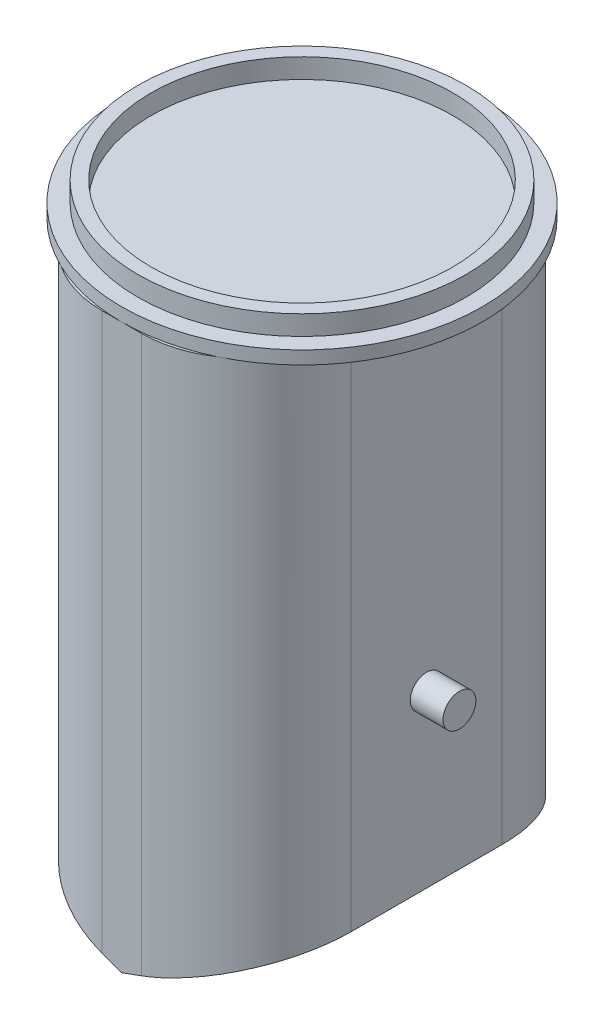
SolidWorks part; units mm, degrees
material "Galvanized Steel"
ref_plane "Front Plane" through (0, 0, 0) normal (0, 0, 1) x (1, 0, 0)
ref_plane "Top Plane" through (0, 0, 0) normal (0, 1, 0) x (1, 0, 0)
ref_plane "Right Plane" through (0, 0, 0) normal (1, 0, 0) x (0, 0, -1)
sketch "Sketch1" plane through (0, 0, 0) normal (0, 1, 0) x (1, 0, 0)
  circle A0 centre (0, 0) radius 27.5
  dimension "D1" = 55
extrude "Boss-Extrude1" add sketch "Sketch1" along normal blind 2
sketch "Sketch2" plane through (0, 2, 0) normal (0, 1, 0) x (1, 0, 0)
  circle A0 centre (0, 0) radius 25
  circle A1 centre (0, 0) radius 23
  dimension "D1" = 50
  dimension "D2" = 46
extrude "Boss-Extrude2" add sketch "Sketch2" along normal blind 3 contours A1
sketch "Sketch3" plane through (0, 0, 0) normal (0, -1, 0) x (1, 0, 0)
  line L5 (19, -27.5) -> (-19, 27.5) construction
  line L6 (33.4253, 0) -> (-33.4253, 0) construction
  line L7 (3, -27.5) -> (-3, -27.5)
  line L8 (19, -11.5) -> (19, 11.5)
  line L9 (3, 27.5) -> (-3, 27.5)
  line L10 (-19, -11.5) -> (-19, 11.5)
  line L11 (19, -27.5) -> (-19, 27.5) construction
  line L12 (19, 27.5) -> (-19, -27.5) construction
  circle A4 centre (0, 0) radius 27.5 construction
  arc A5 (3, -27.5) -> (19, -11.5) centre (3, -11.5) ccw
  arc A6 (-3, -27.5) -> (-19, -11.5) centre (-3, -11.5) cw
  arc A7 (19, 11.5) -> (3, 27.5) centre (3, 11.5) ccw
  arc A8 (-3, 27.5) -> (-19, 11.5) centre (-3, 11.5) ccw
  point P0 (0, 0)
  point P5 (0, 0)
  dimension "D1" = 16
  dimension "D2" = 19
  dimension "D3" = 19
extrude "Boss-Extrude3" add sketch "Sketch3" along normal blind 87
chamfer "Chamfer2" distance 8 angle 70 8 edges at (19, -87, 0) (14.3137, -87, 22.8137) (14.3137, -87, -22.8137) (0, -87, 27.5) (0, -87, -27.5) (-14.3137, -87, 22.8137) (-14.3137, -87, -22.8137) (-19, -87, 0)
sketch "Sketch5" plane through (-19, 0, 0) normal (-1, 0, 0) x (0, 0, 1)
  circle A0 centre (0, -53) radius 2.5
  dimension "D1" = 5
  dimension "D2" = 53
extrude "Boss-Extrude4" add sketch "Sketch5" along normal blind 5
mirror "Mirror1" about plane through (0, 0, 0) normal (1, 0, 0) of "Boss-Extrude4"
